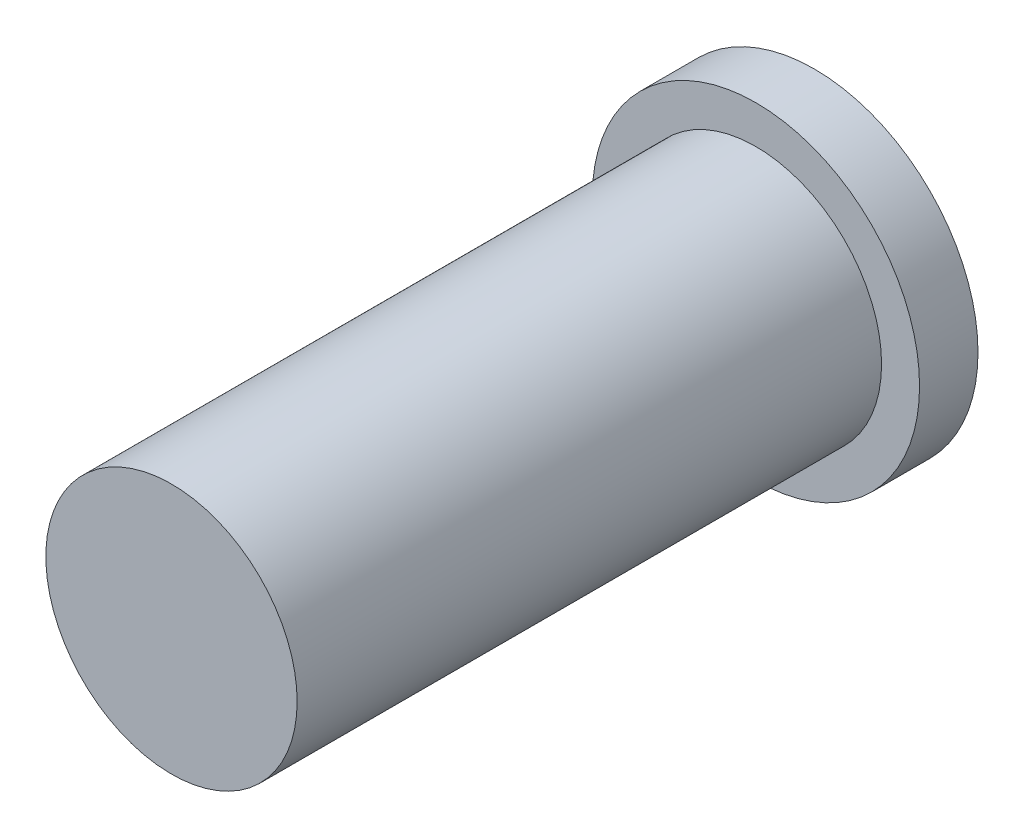
SolidWorks part; units mm, degrees
ref_plane "Oben" through (0, 0, 0) normal (0, 0, 1) x (1, 0, 0)
ref_plane "Vorne" through (0, 0, 0) normal (0, 1, 0) x (1, 0, 0)
ref_plane "Rechts" through (0, 0, 0) normal (1, 0, 0) x (0, 0, -1)
sketch "Skizze1" plane through (0, 0, 0) normal (0, 0, 1) x (1, 0, 0)
  circle A0 centre (0, 0) radius 2.8
  circle A1 centre (0, 0) radius 2.15
  dimension "D1" = 5.6
  dimension "D2" = 4.3
extrude "Aufsatz-Linear austragen1" add sketch "Skizze1" along normal blind 10 contours A1 region at (0, 0, 0)
extrude "Aufsatz-Linear austragen2" add sketch "Skizze1<3>" against normal blind 1 contours A0 A1 | A1 region at (-2.7208, 0, 0) region at (0, 0, 0)
sketch "Skizze1<3>" plane through (0, 0, 0) normal (0, 0, 1) x (1, 0, 0) same geometry as "Skizze1"
